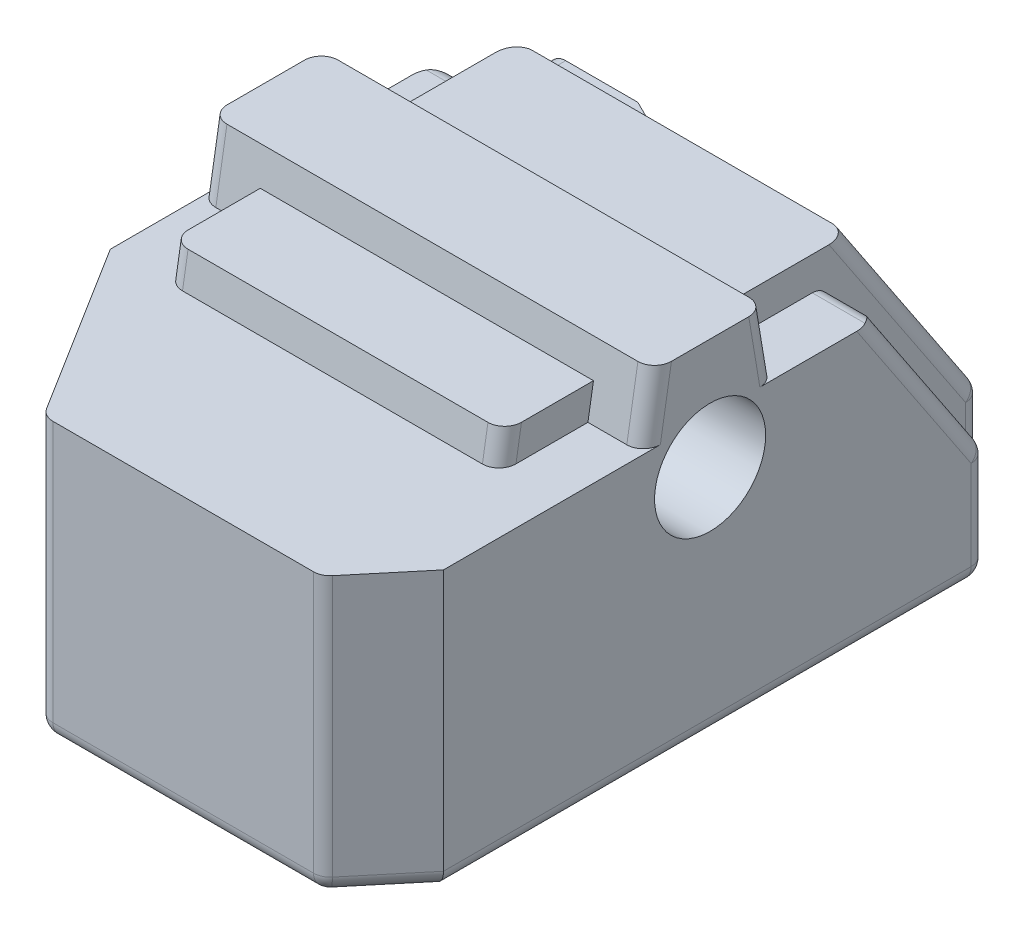
SolidWorks part; units mm, degrees
ref_plane "Front Plane" through (0, 0, 0) normal (0, 0, 1) x (1, 0, 0)
ref_plane "Top Plane" through (0, 0, 0) normal (0, 1, 0) x (1, 0, 0)
ref_plane "Right Plane" through (0, 0, 0) normal (1, 0, 0) x (0, 0, -1)
sketch "Sketch1" plane through (0, 0, 0) normal (1, 0, 0) x (0, 0, -1)
  line L0 (22.5, 12.5) -> (32.5, -2.5)
  line L1 (-22.5, 12.5) -> (22.5, 12.5) construction
  line L2 (-22.5, 12.5) -> (-22.5, -12.5) construction
  line L3 (-22.5, -12.5) -> (22.5, -12.5) construction
  line L4 (22.5, 12.5) -> (22.5, -12.5) construction
  line L5 (-22.5, 12.5) -> (22.5, -12.5) construction
  line L6 (-22.5, -12.5) -> (22.5, 12.5) construction
  line L7 (2.5, 12.5) -> (12.5, 12.5) construction
  line L8 (2.5, 12.5) -> (2.5, 18.5) construction
  line L9 (2.5, 18.5) -> (12.5, 18.5) construction
  line L10 (12.5, 12.5) -> (12.5, 18.5) construction
  line L11 (22.5, -12.5) -> (32.5, -12.5) construction
  line L12 (22.5, -12.5) -> (22.5, -2.5) construction
  line L13 (22.5, -2.5) -> (32.5, -2.5) construction
  line L14 (32.5, -12.5) -> (32.5, -2.5) construction
  line L15 (-22.5, -12.5) -> (32.5, -12.5)
  line L16 (32.5, -2.5) -> (32.5, -12.5)
  line L17 (-22.5, 12.5) -> (-22.5, -12.5)
  line L18 (-22.5, 12.5) -> (1.5, 12.5)
  line L19 (1.5, 12.5) -> (2.5, 18.5)
  line L20 (2.5, 18.5) -> (12.5, 18.5)
  line L21 (12.5, 18.5) -> (13.5, 12.5)
  line L22 (13.5, 12.5) -> (22.5, 12.5)
  line L23 (13, 15.5) -> (25, 15.5)
  line L24 (25, 15.5) -> (37, -2.5)
  line L25 (37, -2.5) -> (37, -11.5)
  line L26 (32.5, -11.5) -> (37, -11.5)
  line L27 (2, 15.5) -> (-6, 15.5)
  line L28 (-6, 15.5) -> (-6.5, 12.5)
  circle A0 centre (7.5, 8.5) radius 5
  point P0 (0, 0)
  point P17 (7.5, 18.5)
  dimension "D11" = 10
  dimension "D1" = 55
  dimension "D2" = 10
  dimension "D3" = 25
  dimension "D4" = 1
  dimension "D5" = 1
  dimension "D6" = 10
  dimension "D7" = 10
  dimension "D8" = 6
  dimension "D9" = 10
  dimension "D10" = 10
  dimension "D12" = 12
  dimension "D13" = 1
  dimension "D14" = 9
  dimension "D15" = 3
  dimension "D16" = 8
extrude "Boss-Extrude1" add sketch "Sketch1" along normal mid plane 40 contours L22 L21 L20 L19 L18 L17 L15 L16 L0 A0 region at (0, -0.1655, -3.5678)
sketch "Sketch2" plane through (0, -12.5, 0) normal (0, -1, 0) x (1, 0, 0)
  line L4 (-20, 22.5) -> (-20, -32.5)
  line L5 (-20, -32.5) -> (20, -32.5)
  line L6 (-20, 22.5) -> (-20, -32.5)
  line L7 (20, 22.5) -> (-20, 22.5)
  line L9 (-20, -32.5) -> (20, -32.5) construction
  line L11 (20, 22.5) -> (-20, 22.5) construction
  line L12 (20, -32.5) -> (20, 22.5)
  line L13 (20, -32.5) -> (20, 22.5)
  circle A0 centre (0, -7.5) radius 10
  point P6 (0, -32.5)
  dimension "D2" = 20
  dimension "D3" = 25
  dimension "D1" = 0
extrude "Boss-Extrude2" add sketch "Sketch1<3>" along normal mid plane 30 contours L16 L26 L25 L24 L23 L21 L22 L0 | L27 L28 L18 L19 region at (0, 4.0231, -28.4897) region at (0, 14, 2.25)
sketch "Sketch1<3>" plane through (0, 0, 0) normal (1, 0, 0) x (0, 0, -1) same geometry as "Sketch1"
sketch "Sketch3" plane through (0, 12.5, 0) normal (0, 1, 0) x (1, 0, 0)
  line L0 (15, -22.5) -> (20, -16.5)
  line L1 (20, -16.5) -> (20, -22.5)
  line L2 (20, -22.5) -> (15, -22.5)
  line L3 (-10, -22.5) -> (-20, -22.5)
  line L4 (-20, -22.5) -> (-20, -6.5)
  line L5 (-20, -6.5) -> (-10, -22.5)
  line L8 (15, 1.5) -> (15, -6.5)
  line L9 (15, -6.5) -> (-15, -6.5)
  line L10 (-15, -6.5) -> (-15, 1.5)
  line L11 (-15, 1.5) -> (-20, 1.5)
  line L12 (-20, 1.5) -> (-20, -22.5)
  line L13 (-20, -22.5) -> (20, -22.5)
  line L14 (20, -22.5) -> (20, 1.5)
  line L15 (20, 1.5) -> (15, 1.5)
  line L16 (15, 1.5) -> (15, -6.5) construction
  line L17 (15, -6.5) -> (-15, -6.5) construction
  line L18 (-15, -6.5) -> (-15, 1.5) construction
  line L19 (-15, 1.5) -> (-20, 1.5) construction
  line L20 (-20, 1.5) -> (-20, -22.5) construction
  line L21 (-20, -22.5) -> (20, -22.5) construction
  line L22 (20, -22.5) -> (20, 1.5) construction
  line L23 (20, 1.5) -> (15, 1.5) construction
  dimension "D2" = 5
  dimension "D3" = 6
  dimension "D4" = 10
  dimension "D5" = 16
  dimension "D1" = 0
extrude "Cut-Extrude2" cut sketch "Sketch3" against normal through all
sketch "Sketch4" plane through (0, 0, 0) normal (0, 0, 1) x (1, 0, 0)
  line L1 (-7, 1.2) -> (-27, 1.2)
  line L2 (-7, 1.2) -> (-7, -8.8)
  line L3 (-7, -8.8) -> (-27, -8.8)
  line L4 (-27, 1.2) -> (-27, -8.8)
  dimension "D1" = 10
  dimension "D2" = 20
  dimension "D3" = 7
  dimension "D4" = 8.8
extrude "Boss-Extrude3" add sketch "Sketch4" against normal blind 20 from offset 20 offset against normal yes
ref_plane "Plane1" through (0, -3.8, 0) normal (0, -1, 0) x (-1, 0, 0)
sketch "Sketch5" plane through (0, -3.8, 0) normal (0, -1, 0) x (-1, 0, 0)
  line L0 (7, 40) -> (19, 40)
  line L1 (27, 40) -> (7, 40) construction
  line L2 (19, 40) -> (7, 34)
  line L3 (7, 40) -> (7, 34)
  dimension "D1" = 6
  dimension "D2" = 12
extrude "Cut-Extrude3" cut sketch "Sketch5" against normal mid plane 10
extrude "Cut-Extrude1" cut sketch "Sketch2" against normal blind 10 contours A0 region at (0, -12.5, -7.5)
fillet "Fillet1" radius 1.5 28 edges at (-10, 0, 22.5) (20, -7.5, -32.5) (15, -7, -37) (4, -2.5, -37) (-15, 8.35, -29.7667) (15, 6.5, -31) (20, 5, -27.5) (-20, 6.85, -26.2667) (-17.5, 12.5, -22.5) (17.5, -2.5, -32.5) (17.5, 12.5, -22.5) (15, 0, 22.5) (-27, -3.8, -20) (0, -12.5, -32.5) (-20, -12.5, -13) (-15, -12.5, 14.5) (2.5, -12.5, 22.5) (17.5, -12.5, 19.5) (20, -12.5, -8) (-15, 14, 6.25) (15, 14, 6.25) (-20, 15.5, -13) (-20, 15.5, -2) (20, 15.5, -2) (20, 15.5, -13) (0, -11.5, -37) (-27, -8.8, -30) (-27, 1.2, -30)
